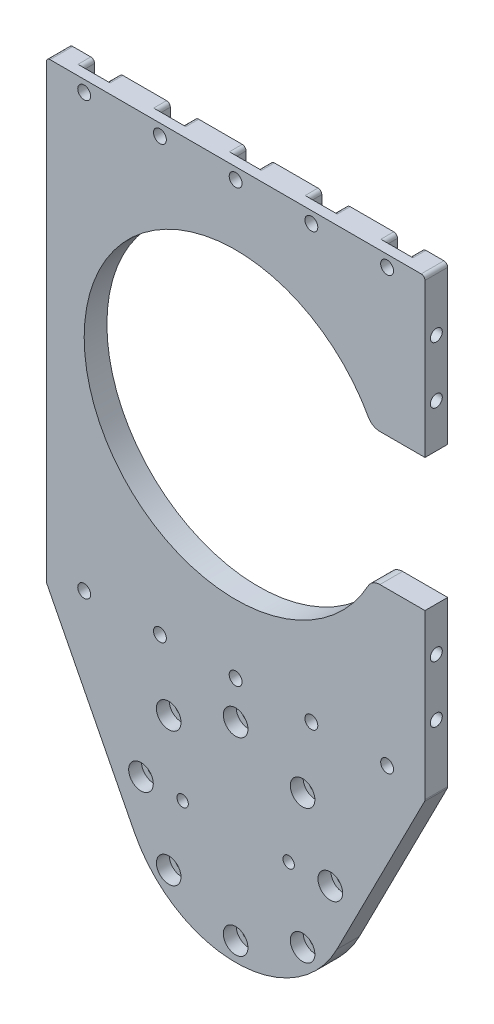
SolidWorks part; units mm, degrees
material "6061-T6 (SS)"
ref_plane "Front Plane" through (0, 0, 0) normal (0, 0, 1) x (1, 0, 0)
ref_plane "Top Plane" through (0, 0, 0) normal (0, 1, 0) x (1, 0, 0)
ref_plane "Right Plane" through (0, 0, 0) normal (1, 0, 0) x (0, 0, -1)
sketch "Sketch1" plane through (0, 0, 0) normal (0, 0, 1) x (1, 0, 0)
  line L0 (-30, 0) -> (-30, 152)
  line L1 (-30, 152) -> (30, 152)
  line L2 (30, 152) -> (30, 0)
  arc A0 (-30, 0) -> (30, 0) centre (0, 0) ccw
  dimension "D1" = 60
  dimension "D2" = 152
extrude "Boss-Extrude1" add sketch "Sketch1" along normal blind 6
sketch "Sketch7" plane through (0, 0, 6) normal (0, 0, 1) x (1, 0, 0)
  line L0 (-50, 32) -> (-26.7242, -13.6315)
  line L1 (30, 152) -> (50, 152)
  line L2 (30, 152) -> (30, 32)
  line L3 (30, 32) -> (50, 32) construction
  line L4 (50, 152) -> (50, 32)
  line L5 (-30, 152) -> (-50, 152)
  line L6 (-30, 152) -> (-30, 32)
  line L7 (-30, 32) -> (-50, 32) construction
  line L8 (-50, 152) -> (-50, 32)
  line L10 (26.7242, -13.6315) -> (50, 32)
  line L13 (30, 0) -> (30, 152)
  line L14 (30, 152) -> (-30, 152)
  line L15 (-30, 152) -> (-30, 0)
  line L16 (30, 0) -> (30, 152)
  line L17 (30, 152) -> (-30, 152)
  line L18 (-30, 152) -> (-30, 0)
  arc A1 (-30, 0) -> (30, 0) centre (0, 0) ccw
  arc A2 (-30, 0) -> (30, 0) centre (0, 0) ccw
  arc M9 (-30, 0) -> (30, 0) centre (0, 0) ccw
  line M10 (30, 0) -> (30, 152)
  line M12 (-30, 152) -> (-30, 0)
  dimension "D1" = 100
  dimension "D2" = 32
  dimension "D3" = 0
  dimension "D4" = 20
extrude "Boss-Extrude2" add sketch "Sketch7" against normal up to surface (6 mm away) contours L5 L8 L0 M9 M12 | L10 L4 L1 M9 M10 region at (-39.5172, 81.611, 6) region at (39.5172, 81.611, 6) up to face at (0, 68.5, 0)
sketch "Sketch2" plane through (0, 0, 6) normal (0, 0, 1) x (1, 0, 0)
  circle A0 centre (0, 0) radius 25
  point P6 (0, 25)
  point P12 (17.6777, 17.6777)
  point P13 (25, 0)
  point P14 (17.6777, -17.6777)
  point P15 (0, -25)
  point P16 (-17.6777, -17.6777)
  point P17 (-25, 0)
  point P18 (-17.6777, 17.6777)
  dimension "D1" = 50
  dimension "D2" = 8
hole_wizard "CBORE for M3 Hex Socket Head Cap Screw1" positions "Sketch2" profile "Sketch3" counterbore size "M3" standard "DIN" end condition through all
sketch "Sketch3" plane through (-17.6777, 17.6777, 6) normal (1, 0, 0) x (0, -1, 0)
  line L0 (0, 0) -> (0, 6)
  line L1 (0, 6) -> (1.7, 6)
  line L3 (1.7, 6) -> (1.7, 3.4)
  line L4 (1.7, 3.4) -> (3.25, 3.4)
  line L5 (3.25, 3.4) -> (3.25, 0)
  line L7 (3.25, 0) -> (0, 0)
  line L11 (0, -6.35) -> (0, 107.95) construction
  dimension "Thru Hole Dia." = 3.4
  dimension "Thru Hole Depth" = 6
  dimension "C'Bore Dia." = 6.5
  dimension "C'Bore Depth" = 3.4
sketch "Sketch4" plane through (0, 0, 0) normal (0, 0, -1) x (-1, 0, 0)
  line L0 (-50, 35) -> (50, 35) construction
  line L3 (-50, 152) -> (50, 152) construction
  line L4 (0, 152) -> (0, 149) construction
  line L8 (50, 32) -> (50, 152) construction
  line L9 (-50, 32) -> (-50, 152) construction
  point P7 (0, 35)
  point P23 (20, 35)
  point P24 (40, 35)
  point P25 (0, 35)
  point P26 (20, 35)
  point P27 (-20, 35)
  point P28 (0, 35)
  point P29 (-20, 35)
  point P30 (-40, 35)
  point P46 (0, 149)
  point P59 (20, 149)
  point P60 (40, 149)
  point P61 (0, 149)
  point P62 (20, 149)
  point P63 (-20, 149)
  point P64 (0, 149)
  point P65 (-20, 149)
  point P66 (-40, 149)
  dimension "D1" = 35
  dimension "D5" = 3
  dimension "D4" = 3
  dimension "D6" = 3
  dimension "D3" = 3
  dimension "D2" = 3
hole_wizard "CBORE for M3 Hex Socket Head Cap Screw2" positions "Sketch4" profile "Sketch6" counterbore size "M3" standard "DIN"
sketch "Sketch6" plane through (40, 149, 0) normal (1, 0, 0) x (0, 1, 0)
  line L0 (0, 0) -> (0, 11.0215)
  line L1 (0, 11.0215) -> (1.7, 10)
  line L2 (1.7, 10) -> (1.7, 3.4)
  line L3 (1.7, 3.4) -> (3.25, 3.4)
  line L4 (3.25, 3.4) -> (3.25, 0)
  line L5 (3.25, 0) -> (0, 0)
  line L10 (0, 11.0215) -> (-1.7, 10) construction
  line L11 (0, -6.35) -> (0, 107.95) construction
  dimension "Hole Dia." = 3.4
  dimension "Hole Depth" = 10
  dimension "C'Bore Dia." = 6.5
  dimension "C'Bore Depth" = 3.4
  dimension "Drill Angle" = 118
sketch "Sketch8" plane through (0, 0, 0) normal (0, 0, -1) x (-1, 0, 0)
  line L7 (50, 32) -> (50, 152) construction
  line L8 (-50, 110.5) -> (-35.9687, 110.5)
  line L9 (-50, 32) -> (-50, 152) construction
  line L11 (-35.9687, 75.5) -> (-50, 75.5)
  line L12 (-50, 75.5) -> (-50, 110.5)
  line L13 (-35.9687, 110.5) -> (-35.9687, 75.5) construction
  arc A0 (-35.9687, 75.5) -> (-35.9687, 110.5) centre (0, 93) ccw
  dimension "D2" = 93
  dimension "D3" = 80
  dimension "D1" = 50
  dimension "D4" = 35
extrude "Cut-Extrude1" cut sketch "Sketch8" against normal up to next and the other way through all
sketch "Sketch11" plane through (0, 0, 0) normal (0, 0, -1) x (-1, 0, 0)
  circle A0 centre (0, 0) radius 14
  point P6 (-14, 0)
  point P8 (14, 0)
  dimension "D1" = 28
hole_wizard "Ø3.0mm Dowel Hole1" positions "Sketch11" profile "Sketch10" hole size "Ø3.0" standard "BSI" end condition through all
sketch "Sketch10" plane through (-14, 0, 0) normal (1, 0, 0) x (0, 1, 0)
  line L0 (0, 0) -> (0, 6)
  line L1 (0, 6) -> (1.5, 6)
  line L2 (1.5, 6) -> (1.5, 0)
  line L5 (1.5, 0) -> (0, 0)
  line L11 (0, -6.35) -> (0, 107.95) construction
  dimension "Thru Hole Dia." = 3
  dimension "Thru Hole Depth" = 6
sketch "Sketch12" plane through (0, 0, 0) normal (0, 0, -1) x (-1, 0, 0)
  line L0 (-43.25, 149) -> (-43.25, 152)
  line L1 (-43.25, 152) -> (-36.75, 152)
  line L2 (-36.75, 152) -> (-36.75, 149)
  line L3 (-38.75, 152) -> (-21.25, 152) construction
  line L4 (-23.25, 149) -> (-23.25, 152)
  line L5 (-23.25, 152) -> (-16.75, 152)
  line L6 (-16.75, 152) -> (-16.75, 149)
  line L7 (-3.25, 149) -> (-3.25, 152)
  line L8 (-3.25, 152) -> (3.25, 152)
  line L9 (3.25, 152) -> (3.25, 149)
  line L10 (16.75, 149) -> (16.75, 152)
  line L11 (16.75, 152) -> (23.25, 152)
  line L12 (23.25, 152) -> (23.25, 149)
  line L13 (36.75, 149) -> (36.75, 152)
  line L14 (36.75, 152) -> (43.25, 152)
  line L15 (43.25, 152) -> (43.25, 149)
  arc A0 (-41.25, 152) -> (-38.75, 152) centre (-40, 149) ccw construction
  arc A1 (-41.25, 152) -> (-38.75, 152) centre (-40, 149) ccw construction
  arc A2 (-43.25, 149) -> (-36.75, 149) centre (-40, 149) ccw
  arc A5 (-23.25, 149) -> (-16.75, 149) centre (-20, 149) ccw
  arc A6 (-3.25, 149) -> (3.25, 149) centre (0, 149) ccw
  arc A7 (16.75, 149) -> (23.25, 149) centre (20, 149) ccw
  arc A8 (36.75, 149) -> (43.25, 149) centre (40, 149) ccw
  dimension "D1" = 5
extrude "Cut-Extrude2" cut sketch "Sketch12" against normal up to surface (3.4 mm away) and the other way through all up to face at (38.3, 149, 3.4)
fillet "Fillet3" radius 1 14 edges at (23.25, 152, 1.7) (16.75, 152, 1.7) (3.25, 152, 1.7) (-3.25, 152, 1.7) (-16.75, 152, 1.7) (-23.25, 152, 1.7) (-36.75, 152, 1.7) (-43.25, 152, 1.7) (-50, 152, 3) (-50, 32, 3) (50, 32, 3) (50, 152, 3) (36.75, 152, 1.7) (43.25, 152, 1.7)
sketch "Sketch15" plane through (50, 0, 0) normal (1, 0, 0) x (0, 0, -1)
  line L0 (-3, 110.5) -> (-3, 75.5) construction
  line L2 (-6, 75.5) -> (-3, 75.5) construction
  line L4 (-6, 110.5) -> (19.2728, 110.5) construction
  line L5 (-6, 151) -> (-6, 110.5) construction
  line L6 (0, 110.5) -> (-6, 110.5) construction
  line L8 (-3, 93) -> (37.8118, 93) construction
  point P7 (-3, 137)
  point P9 (-3, 122)
  point P35 (0, 0)
  point P36 (-3, 64)
  point P37 (-3, 49)
  dimension "D2" = 15
hole_wizard "Tap Drill for M3 Helicoil1" positions "Sketch15" profile "Sketch14" hole size "M3x0.5" standard "DIN"
sketch "Sketch14" plane through (50, 137, 3) normal (0, 1, 0) x (0, 0, -1)
  line L0 (0, 0) -> (0, 15.9464)
  line L1 (0, 15.9464) -> (1.575, 15)
  line L2 (1.575, 15) -> (1.575, 0)
  line L5 (1.575, 0) -> (0, 0)
  line L10 (0, 15.9464) -> (-1.575, 15) construction
  line L11 (0, -6.35) -> (0, 107.95) construction
  dimension "Hole Dia." = 3.15
  dimension "Hole Depth" = 15
  dimension "Drill Angle" = 118
fillet "Fillet4" radius 3.5 2 edges at (35.9687, 75.5, 3) (35.9687, 110.5, 3)
